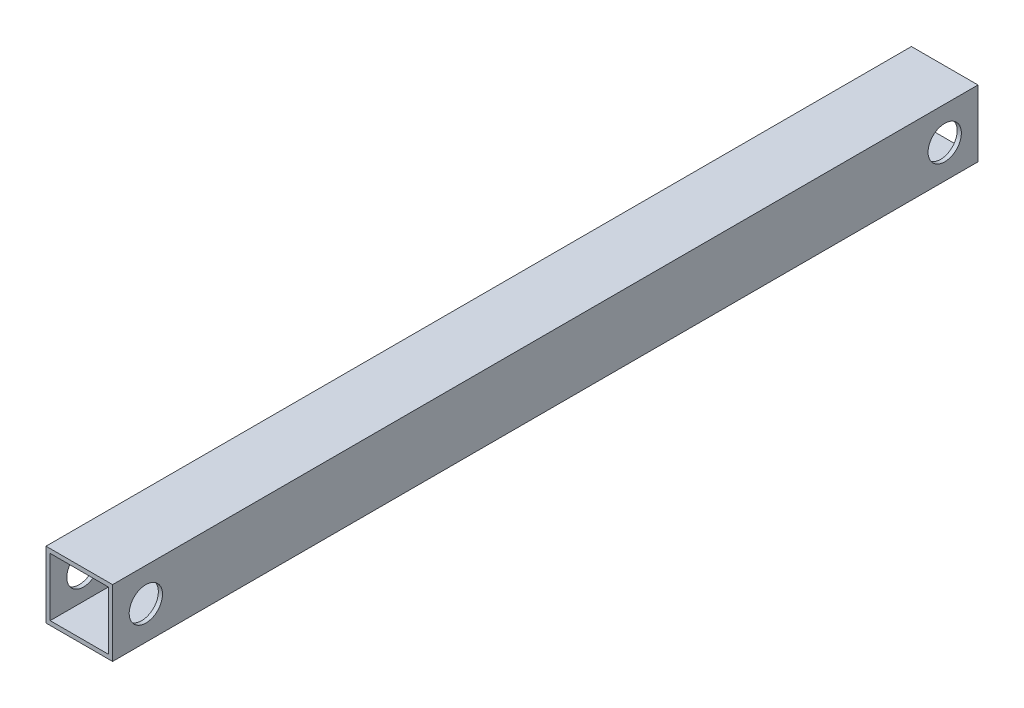
SolidWorks part; units mm, degrees
ref_plane "Front Plane" through (0, 0, 0) normal (0, 0, 1) x (1, 0, 0)
ref_plane "Top Plane" through (0, 0, 0) normal (0, 1, 0) x (1, 0, 0)
ref_plane "Right Plane" through (0, 0, 0) normal (1, 0, 0) x (0, 0, -1)
sketch "Sketch1" plane through (0, 0, 0) normal (0, 0, 1) x (1, 0, 0)
  line L1 (12.7, -12.7) -> (-12.7, -12.7)
  line L2 (12.7, -12.7) -> (12.7, 12.7)
  line L3 (12.7, 12.7) -> (-12.7, 12.7)
  line L4 (-12.7, -12.7) -> (-12.7, 12.7)
  line L5 (12.7, -12.7) -> (-12.7, 12.7) construction
  line L6 (12.7, 12.7) -> (-12.7, -12.7) construction
  point P0 (0, 0)
  dimension "D1" = 25.4
extrude "Extrude-Thin1" add sketch "Sketch1" along normal mid plane 330.2 thin thin type one direction reverse wall 1.5875
sketch "Sketch2" plane through (12.7, 0, 0) normal (1, 0, 0) x (0, 0, -1)
  line L0 (-152.4, 12.7) -> (-152.4, 0) construction
  line L1 (-165.1, 12.7) -> (165.1, 12.7) construction
  line L2 (-152.4, 0) -> (-152.4, -12.7) construction
  line L3 (-165.1, -12.7) -> (165.1, -12.7) construction
  line L4 (-165.1, -12.7) -> (-165.1, 12.7) construction
  line L5 (0, 12.7) -> (0, -12.7) construction
  line L6 (152.4, 0) -> (152.4, -12.7) construction
  line L7 (152.4, 12.7) -> (152.4, 0) construction
  circle A0 centre (-152.4, 0) radius 6.35
  circle A1 centre (152.4, 0) radius 6.35
  dimension "D1" = 12.7
  dimension "D2" = 12.7
extrude "Cut-Extrude1" cut sketch "Sketch2" against normal through all
